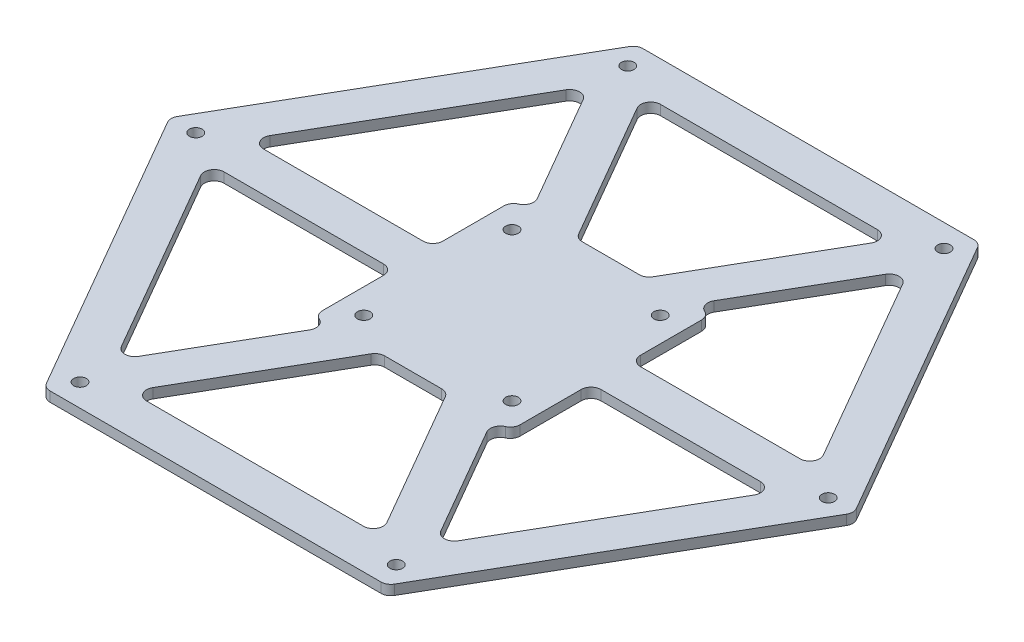
SolidWorks part; units mm, degrees
material "6061-T6 (SS)"
ref_plane "Front Plane" through (0, 0, 0) normal (0, 0, 1) x (1, 0, 0)
ref_plane "Top Plane" through (0, 0, 0) normal (0, 1, 0) x (1, 0, 0)
ref_plane "Right Plane" through (0, 0, 0) normal (1, 0, 0) x (0, 0, -1)
sketch "Sketch1" plane through (0, 0, 0) normal (0, 1, 0) x (1, 0, 0)
  line L0 (-75.0555, 130) -> (-150.1111, 0) construction
  line L7 (171.7617, 2.5) -> (88.0459, 147.5)
  line L8 (83.7158, 150) -> (-83.7158, 150)
  line L9 (-88.0459, 147.5) -> (-171.7617, 2.5)
  line L10 (-171.7617, -2.5) -> (-88.0459, -147.5)
  line L11 (-83.7158, -150) -> (83.7158, -150)
  line L12 (88.0459, -147.5) -> (171.7617, -2.5)
  line L13 (-76.4989, 112.5) -> (-8.6603, -5)
  line L14 (-59.1784, 122.5) -> (8.6603, 5)
  line L15 (-85.1592, 112.5) -> (-140.0074, 17.5)
  line L16 (-140.0074, -17.5) -> (-85.1592, -112.5)
  line L17 (-54.8483, -130) -> (54.8483, -130)
  line L18 (85.1592, -112.5) -> (140.0074, -17.5)
  line L19 (140.0074, 17.5) -> (85.1592, 112.5)
  line L20 (54.8483, 130) -> (-54.8483, 130)
  line L21 (75.0555, 130) -> (-75.0555, 130) construction
  line L22 (150.1111, 0) -> (75.0555, 130) construction
  line L23 (-150.1111, 0) -> (-75.0555, -130) construction
  line L24 (-75.0555, -130) -> (75.0555, -130) construction
  line L25 (75.0555, -130) -> (150.1111, 0) construction
  line L26 (59.1784, 122.5) -> (-8.6603, 5)
  line L27 (76.4989, 112.5) -> (8.6603, -5)
  line L28 (54.8483, 130) -> (-54.8483, 130)
  line L29 (140.0074, 17.5) -> (85.1592, 112.5)
  line L30 (135.6773, 10) -> (0, 10)
  line L31 (135.6773, -10) -> (0, -10)
  line L32 (140.0074, 17.5) -> (85.1592, 112.5)
  line L33 (85.1592, -112.5) -> (140.0074, -17.5)
  line L34 (76.4989, -112.5) -> (8.6603, 5)
  line L35 (59.1784, -122.5) -> (-8.6603, -5)
  line L36 (85.1592, -112.5) -> (140.0074, -17.5)
  line L37 (-54.8483, -130) -> (54.8483, -130)
  line L38 (-59.1784, -122.5) -> (8.6603, -5)
  line L39 (-76.4989, -112.5) -> (-8.6603, 5)
  line L40 (-54.8483, -130) -> (54.8483, -130)
  line L41 (-140.0074, -17.5) -> (-85.1592, -112.5)
  line L42 (-135.6773, -10) -> (0, -10)
  line L43 (-135.6773, 10) -> (0, 10)
  line L44 (-140.0074, -17.5) -> (-85.1592, -112.5)
  line L45 (-85.1592, 112.5) -> (-140.0074, 17.5)
  line L47 (-50, -50) -> (50, -50)
  line L48 (-50, -50) -> (-50, 50)
  line L49 (-50, 50) -> (50, 50)
  line L50 (50, -50) -> (50, 50)
  line L51 (-50, -50) -> (50, 50) construction
  line L52 (-50, 50) -> (50, -50) construction
  circle A1 centre (0, 0) radius 173.2051 construction
  circle A2 centre (-80, 138.5641) radius 3.2
  circle A3 centre (80, 138.5641) radius 3.2
  circle A4 centre (160, 0) radius 3.2
  circle A5 centre (80, -138.5641) radius 3.2
  circle A6 centre (-80, -138.5641) radius 3.2
  circle A7 centre (-160, 0) radius 3.2
  arc A8 (83.7158, -150) -> (88.0459, -147.5) centre (83.7158, -145) ccw
  arc A9 (-88.0459, -147.5) -> (-83.7158, -150) centre (-83.7158, -145) ccw
  arc A10 (-171.7617, 2.5) -> (-171.7617, -2.5) centre (-167.4316, 0) ccw
  arc A11 (171.7617, 2.5) -> (171.7617, -2.5) centre (167.4316, 0) cw
  arc A12 (88.0459, 147.5) -> (83.7158, 150) centre (83.7158, 145) ccw
  arc A13 (-83.7158, 150) -> (-88.0459, 147.5) centre (-83.7158, 145) ccw
  arc A20 (-75.0555, 130) -> (-75.0555, 130) centre (-75.0555, 130) ccw
  arc A21 (-76.4989, 112.5) -> (-85.1592, 112.5) centre (-80.829, 110) ccw
  arc A22 (-54.8483, 130) -> (-59.1784, 122.5) centre (-54.8483, 125) ccw
  arc A24 (75.0555, 130) -> (75.0555, 130) centre (75.0555, 130) ccw construction
  arc A26 (-150.1111, 0) -> (-150.1111, 0) centre (-150.1111, 0) ccw construction
  arc A28 (-75.0555, -130) -> (-75.0555, -130) centre (-75.0555, -130) ccw construction
  arc A30 (75.0555, -130) -> (75.0555, -130) centre (75.0555, -130) ccw construction
  arc A32 (150.1111, 0) -> (150.1111, 0) centre (150.1111, 0) cw construction
  arc A33 (59.1784, 122.5) -> (54.8483, 130) centre (54.8483, 125) ccw
  arc A34 (85.1592, 112.5) -> (76.4989, 112.5) centre (80.829, 110) ccw
  arc A35 (135.6773, 10) -> (140.0074, 17.5) centre (135.6773, 15) ccw
  arc A36 (140.0074, -17.5) -> (135.6773, -10) centre (135.6773, -15) ccw
  arc A37 (76.4989, -112.5) -> (85.1592, -112.5) centre (80.829, -110) ccw
  arc A38 (54.8483, -130) -> (59.1784, -122.5) centre (54.8483, -125) ccw
  arc A39 (-59.1784, -122.5) -> (-54.8483, -130) centre (-54.8483, -125) ccw
  arc A40 (-85.1592, -112.5) -> (-76.4989, -112.5) centre (-80.829, -110) ccw
  arc A41 (-135.6773, -10) -> (-140.0074, -17.5) centre (-135.6773, -15) ccw
  arc A42 (-140.0074, 17.5) -> (-135.6773, 10) centre (-135.6773, 15) ccw
  point P5 (86.6025, -150)
  point P25 (0, 0)
  point P27 (-86.6025, -150)
  point P30 (-173.2051, 0)
  point P33 (173.2051, 0)
  point P36 (86.6025, 150)
  point P39 (-86.6025, 150)
  point P134 (0, 0)
  dimension "D2" = 6
  dimension "D3" = 5
  dimension "D4" = 5
  dimension "D5" = 5
  dimension "D1" = 300
  dimension "D10" = 100
  dimension "D11" = 100
  dimension "D6" = 20
  dimension "D9" = 6
extrude "Boss-Extrude1" add sketch "Sketch1" along normal blind 10 contours L8 A13 L9 A10 L10 A9 L11 A8 L12 A11 L7 A12 A42 L15 A21 L13 L49 L14 A22 L20 A33 L26 L27 A34 L19 A35 L30 L50 L31 A36 L18 A37 L34 L47 L35 A38 L17 A39 L38 L39 A40 L16 A41 L42 L48 L43 A2 region at (167.8607, 0, 0)
sketch "Sketch2" plane through (0, 0, 0) normal (0, 1, 0) x (1, 0, 0)
  line L1 (-50, -50) -> (50, -50)
  line L2 (-50, -50) -> (-50, 50)
  line L3 (-50, 50) -> (50, 50)
  line L4 (50, -50) -> (50, 50)
  line L5 (-50, -50) -> (50, 50) construction
  line L6 (-50, 50) -> (50, -50) construction
  point P0 (0, 0)
  dimension "D1" = 100
  dimension "D2" = 100
extrude "Boss-Extrude2" add sketch "Sketch2" along normal blind 10
fillet "Fillet1" radius 5 12 edges at (-17.3205, 5, -50) (17.3205, 5, -50) (40.4145, 5, -50) (50, 5, -10) (50, 5, 10) (40.4145, 5, 50) (-17.3205, 5, 50) (17.3205, 5, 50) (-40.4145, 5, -50) (-50, 5, -10) (-50, 5, 10) (-40.4145, 5, 50)
fillet "Fillet2" radius 5 4 edges at (-50, 5, -50) (-50, 5, 50) (50, 5, 50) (50, 5, -50)
sketch "Sketch3" plane through (0, 10, 0) normal (0, 1, 0) x (1, 0, 0)
  line L5 (-37.5, -37.5) -> (37.5, 37.5) construction
  line L6 (-37.5, 37.5) -> (37.5, -37.5) construction
  circle A0 centre (-37.5, 37.5) radius 3.2
  circle A1 centre (37.5, 37.5) radius 3.2
  circle A2 centre (37.5, -37.5) radius 3.2
  circle A3 centre (-37.5, -37.5) radius 3.2
  point P0 (0, 0)
  dimension "D1" = 75
  dimension "D2" = 75
extrude "Cut-Extrude2" cut sketch "Sketch3" against normal blind 10
sketch "Sketch6" plane through (0, 10, 0) normal (0, 1, 0) x (1, 0, 0)
  line L0 (88.0459, 147.5) -> (171.7617, 2.5)
  line L1 (88.0459, 147.5) -> (171.7617, 2.5)
  line L2 (171.7617, -2.5) -> (88.0459, -147.5)
  line L3 (171.7617, -2.5) -> (88.0459, -147.5)
  line L4 (83.7158, -150) -> (-83.7158, -150)
  line L5 (83.7158, -150) -> (-83.7158, -150)
  line L6 (-88.0459, -147.5) -> (-171.7617, -2.5)
  line L7 (-88.0459, -147.5) -> (-171.7617, -2.5)
  line L8 (-171.7617, 2.5) -> (-88.0459, 147.5)
  line L9 (-171.7617, 2.5) -> (-88.0459, 147.5)
  line L10 (-83.7158, 150) -> (83.7158, 150)
  line L11 (-83.7158, 150) -> (83.7158, 150)
  arc A0 (88.0459, 147.5) -> (83.7158, 150) centre (83.7158, 145) ccw
  arc A1 (88.0459, 147.5) -> (83.7158, 150) centre (83.7158, 145) ccw
  arc A2 (171.7617, -2.5) -> (171.7617, 2.5) centre (167.4316, 0) ccw
  arc A3 (171.7617, -2.5) -> (171.7617, 2.5) centre (167.4316, 0) ccw
  arc A4 (83.7158, -150) -> (88.0459, -147.5) centre (83.7158, -145) ccw
  arc A5 (83.7158, -150) -> (88.0459, -147.5) centre (83.7158, -145) ccw
  arc A6 (-88.0459, -147.5) -> (-83.7158, -150) centre (-83.7158, -145) ccw
  arc A7 (-88.0459, -147.5) -> (-83.7158, -150) centre (-83.7158, -145) ccw
  arc A8 (-171.7617, 2.5) -> (-171.7617, -2.5) centre (-167.4316, 0) ccw
  arc A9 (-171.7617, 2.5) -> (-171.7617, -2.5) centre (-167.4316, 0) ccw
  arc A10 (-83.7158, 150) -> (-88.0459, 147.5) centre (-83.7158, 145) ccw
  arc A11 (-83.7158, 150) -> (-88.0459, 147.5) centre (-83.7158, 145) ccw
extrude "Cut-Extrude3" cut sketch "Sketch6" against normal blind 5
